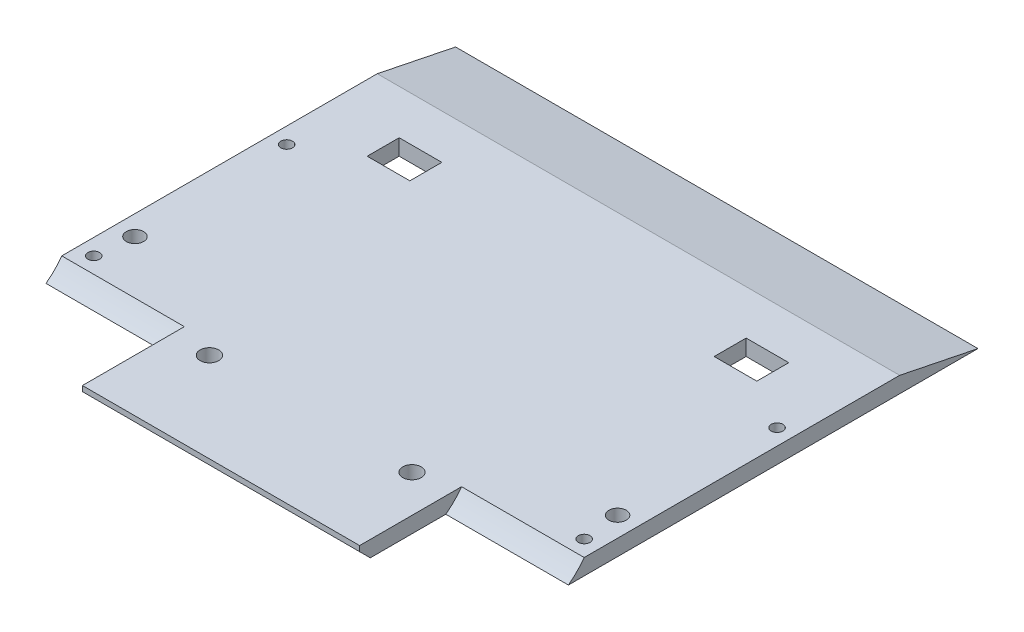
SolidWorks part; units mm, degrees
ref_plane "Alzado" through (0, 0, 0) normal (0, 0, 1) x (1, 0, 0)
ref_plane "Planta" through (0, 0, 0) normal (0, 1, 0) x (1, 0, 0)
ref_plane "Vista lateral" through (0, 0, 0) normal (1, 0, 0) x (0, 0, -1)
sketch "Croquis1" plane through (0, 0, 0) normal (0, 1, 0) x (1, 0, 0)
  line L1 (-46.8887, 38.0954) -> (51.1113, 38.0954)
  line L2 (-46.8887, 38.0954) -> (-46.8887, -59.9046)
  line L3 (-46.8887, -59.9046) -> (51.1113, -59.9046)
  line L4 (51.1113, 38.0954) -> (51.1113, -59.9046)
  line L5 (-46.8887, -59.9046) -> (-23.8887, -59.9046)
  line L6 (-46.8887, -59.9046) -> (-46.8887, -36.9046)
  line L7 (-46.8887, -36.9046) -> (-23.8887, -36.9046)
  line L8 (-23.8887, -59.9046) -> (-23.8887, -36.9046)
  line L9 (51.1113, -59.9046) -> (28.1113, -59.9046)
  line L10 (51.1113, -59.9046) -> (51.1113, -36.9046)
  line L11 (51.1113, -36.9046) -> (28.1113, -36.9046)
  line L12 (28.1113, -59.9046) -> (28.1113, -36.9046)
  line L13 (28.1113, -54.9046) -> (-23.8887, -54.9046)
  line L14 (28.1113, -54.9046) -> (28.1113, -59.9046)
  line L15 (28.1113, -59.9046) -> (-23.8887, -59.9046)
  line L16 (-23.8887, -54.9046) -> (-23.8887, -59.9046)
  dimension "D1" = 98
  dimension "D2" = 98
  dimension "D3" = 23
  dimension "D4" = 23
  dimension "D5" = 18
  dimension "D6" = 23
  dimension "D7" = 23
extrude "Saliente-Extruir1" add sketch "Croquis1" along normal blind 3 contours L13 L12 L11 L4 L1 L2 L7 L8 region at (2.1113, 0, 4.6573)
sketch "Croquis2" plane through (-46.8887, 0, 0) normal (-1, 0, 0) x (0, 0, 1)
  line L0 (-38.0954, 0) -> (-23.3984, 3)
  line L1 (-38.0954, 3) -> (36.9046, 3) construction
  line L2 (36.9046, 0) -> (54.9046, 0)
  line L3 (54.9046, 3) -> (39.9046, 3)
  line L4 (54.9046, 3) -> (54.9046, 15)
  line L5 (54.9046, 15) -> (39.9046, 15)
  line L6 (39.9046, 3) -> (39.9046, 15)
  line L7 (-38.0954, 0) -> (36.9046, 0) construction
  circle A0 centre (46.9046, 11) radius 13
  circle A1 centre (46.9046, 11) radius 13.7
  line M5 (36.9046, 0) -> (36.9046, 3)
  line M6 (36.9046, 3) -> (-38.0954, 3)
  line M7 (-38.0954, 3) -> (-38.0954, 0)
  dimension "D3" = 26
  dimension "D5" = 85
  dimension "D6" = 0.7
  dimension "D1" = 12
  dimension "D2" = 15
  dimension "D4" = 8
  dimension "D7" = 15
  dimension "D8" = 11.537
extrude "Cortar-Extruir1" cut sketch "Croquis2" against normal blind 102 contours L0 M7 M6 region at (-46.8887, 2, -33.1964)
extrude "Saliente-Extruir2" add sketch "Croquis2<4>" against normal blind 98 contours A1 L2 M5 region at (-46.8887, 0.5288, 37.4972)
sketch "Croquis2<4>" plane through (-46.8887, 0, 0) normal (-1, 0, 0) x (0, 0, 1) same geometry as "Croquis2"
extrude "Cortar-Extruir2" cut sketch "Croquis2<5>" against normal blind 23 contours A1 A0 M6 M5 | A0 M6 M5 region at (-46.8887, 2.5172, 36.5075) region at (-46.8887, 2.8973, 36.8219)
sketch "Croquis2<5>" plane through (-46.8887, 0, 0) normal (-1, 0, 0) x (0, 0, 1) same geometry as "Croquis2"
extrude "Cortar-Extruir3" cut sketch "Croquis2<6>" against normal blind 23 from surface contours A1 A0 M6 M5 | A0 M6 M5 region at (-46.8887, 2.5172, 36.5075) region at (-46.8887, 2.8973, 36.8219) starting at face at (28.1113, 1.5189, 44.464)
sketch "Croquis2<6>" plane through (-46.8887, 0, 0) normal (-1, 0, 0) x (0, 0, 1) same geometry as "Croquis2"
chamfer "Chaflán1" distance 2 angle 45 1 edges at (2.1113, 0, 54.9046)
sketch "Croquis3" plane through (0, 3, 0) normal (0, 1, 0) x (1, 0, 0)
  line L0 (-46.8887, 23.3984) -> (-46.8887, -35.783) construction
  line L1 (-43.8887, 3.3984) -> (48.1113, 3.3984) construction
  line L2 (-43.8887, 3.3984) -> (-43.8887, -32.783) construction
  line L3 (-43.8887, -32.783) -> (48.1113, -32.783) construction
  line L4 (48.1113, 3.3984) -> (48.1113, -32.783) construction
  line L5 (51.1113, 23.3984) -> (51.1113, -35.783) construction
  line L6 (51.1113, -35.783) -> (28.1113, -35.783) construction
  line L7 (51.1113, 23.3984) -> (-46.8887, 23.3984) construction
  circle A0 centre (-43.8887, 3.3984) radius 1.1
  circle A1 centre (-43.8887, -32.783) radius 1.1
  circle A2 centre (48.1113, -32.783) radius 1.1
  circle A3 centre (48.1113, 3.3984) radius 1.1
  dimension "D5" = 2.2
  dimension "D6" = 2.2
  dimension "D7" = 2.2
  dimension "D8" = 2.2
  dimension "D1" = 3
  dimension "D2" = 3
  dimension "D3" = 3
  dimension "D4" = 20
extrude "Cortar-Extruir4" cut sketch "Croquis3" against normal blind 23
sketch "Croquis5" plane through (0, 3, 0) normal (0, 1, 0) x (1, 0, 0)
  circle A0 centre (-16.8887, -38.0816) radius 1.75
  circle A1 centre (21.1113, -38.0816) radius 1.75
extrude "Cortar-Extruir5" cut sketch "Croquis5" against normal blind 52
sketch "Croquis6" plane through (0, 3, 0) normal (0, 1, 0) x (1, 0, 0)
  circle A0 centre (-43.1587, -25.7816) radius 1.6245
  circle A1 centre (47.3813, -25.7816) radius 1.6245
extrude "Cortar-Extruir6" cut sketch "Croquis6" against normal blind 4 contours A1
sketch "Croquis7" plane through (0, 3, 0) normal (0, 1, 0) x (1, 0, 0)
  circle A0 centre (-43.1587, -25.7816) radius 1.6245
extrude "Cortar-Extruir7" cut sketch "Croquis7" against normal blind 4
sketch "Croquis8" plane through (0, 3, 0) normal (0, 1, 0) x (1, 0, 0)
  line L0 (-25.4322, 16.0573) -> (-35.4322, 16.0573) construction
  line L1 (-34.4322, 15.0573) -> (-26.4322, 15.0573)
  line L2 (-34.4322, 15.0573) -> (-34.4322, 9.0573)
  line L3 (-34.4322, 9.0573) -> (-26.4322, 9.0573)
  line L4 (-26.4322, 15.0573) -> (-26.4322, 9.0573)
  line L5 (30.6548, 15.0573) -> (38.6548, 15.0573)
  line L6 (30.6548, 15.0573) -> (30.6548, 9.0573)
  line L7 (30.6548, 9.0573) -> (38.6548, 9.0573)
  line L8 (38.6548, 15.0573) -> (38.6548, 9.0573)
  line L9 (-35.4322, 8.0573) -> (-25.4322, 8.0573) construction
  line L10 (-35.4322, 16.0573) -> (-35.4322, 8.0573) construction
  line L11 (-25.4322, 8.0573) -> (-25.4322, 16.0573) construction
  line L12 (29.6548, 16.0573) -> (29.6548, 8.0573) construction
  line L13 (39.6548, 16.0573) -> (29.6548, 16.0573) construction
  line L14 (29.6548, 8.0573) -> (39.6548, 8.0573) construction
  line L15 (39.6548, 8.0573) -> (39.6548, 16.0573) construction
  point P10 (-30.4322, 16.0573)
  point P17 (-25.4322, 12.0573)
  point P24 (34.6548, 8.0573)
  dimension "D1" = 1
  dimension "D2" = 1
  dimension "D3" = 1
  dimension "D4" = 1
  dimension "D5" = 1
  dimension "D6" = 1
  dimension "D7" = 1
  dimension "D8" = 1
extrude "Cortar-Extruir8" cut sketch "Croquis8" against normal blind 4
sketch "Croquis9" plane through (0, 3, 0) normal (0, 1, 0) x (1, 0, 0)
  line L1 (-46.8887, 23.3984) -> (51.1113, 23.3984)
  line L2 (-46.8887, 23.3984) -> (-46.8887, -35.783)
  line L3 (-46.8887, -35.783) -> (51.1113, -35.783)
  line L4 (51.1113, 23.3984) -> (51.1113, -35.783)
  dimension "D1" = 59.1815
  dimension "D2" = 98
